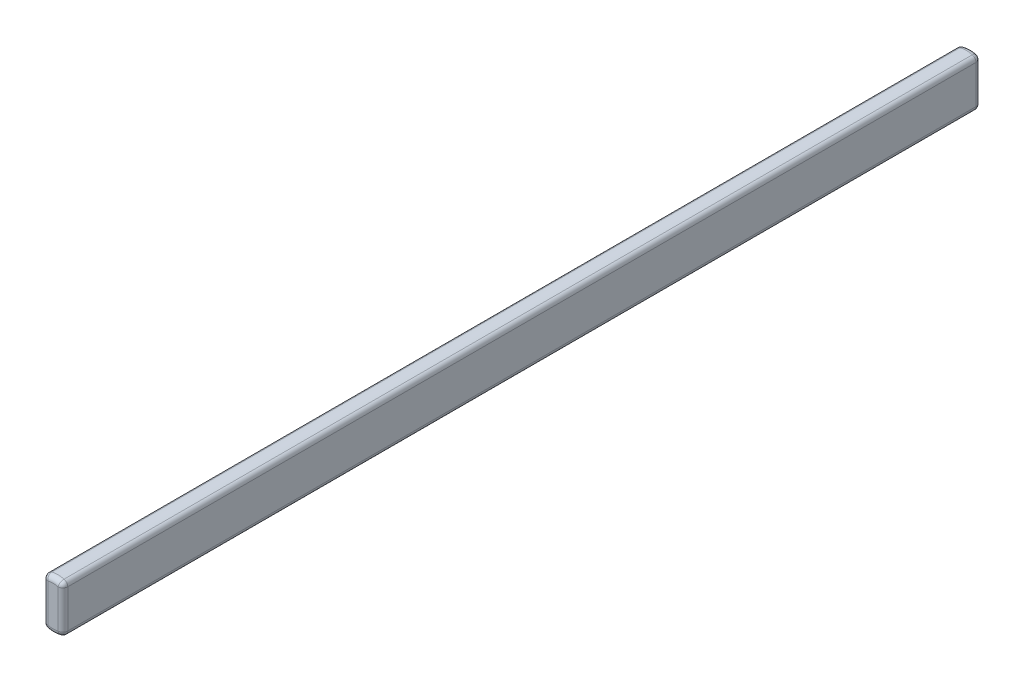
SolidWorks part; units mm, degrees
material "PET"
ref_plane "Front Plane" through (0, 0, 0) normal (0, 0, 1) x (1, 0, 0)
ref_plane "Top Plane" through (0, 0, 0) normal (0, 1, 0) x (1, 0, 0)
ref_plane "Right Plane" through (0, 0, 0) normal (1, 0, 0) x (0, 0, -1)
sketch "Sketch1" plane through (0, 0, 0) normal (0, 0, 1) x (1, 0, 0)
  circle A0 centre (0, 0) radius 5
  dimension "D1" = 10
extrude "Boss-Extrude1" add sketch "Sketch1" along normal blind 170
sketch "Sketch2" plane through (0, 0, 0) normal (0, 0, -1) x (-1, 0, 0)
  line L1 (-2, -4.5826) -> (2, -4.5826) construction
  line L2 (-2, -4.5826) -> (-2, 4.5826)
  line L3 (-2, 4.5826) -> (2, 4.5826) construction
  line L4 (2, -4.5826) -> (2, 4.5826)
  line L5 (-2, -4.5826) -> (2, 4.5826) construction
  line L6 (-2, 4.5826) -> (2, -4.5826) construction
  arc A1 (2, 4.5826) -> (-2, 4.5826) centre (0, 0) ccw
  circle A2 centre (0, 0) radius 5
  arc A3 (-2, -4.5826) -> (2, -4.5826) centre (0, 0) ccw
  dimension "D1" = 0
  dimension "D2" = 4
extrude "Boss-Extrude2" add sketch "Sketch2" along normal blind 8
sketch "Sketch5" plane through (0, 0, 170) normal (0, 0, 1) x (1, 0, 0)
  line L4 (2, -4.5826) -> (2, 4.5826)
  line L5 (-2, 4.5826) -> (-2, -4.5826)
  circle A0 centre (0, 0) radius 5 construction
  arc A4 (2, 4.5826) -> (-2, 4.5826) centre (0, 0) ccw
  arc A5 (-2, -4.5826) -> (2, -4.5826) centre (0, 0) ccw
  dimension "D1" = 4
extrude "Boss-Extrude3" add sketch "Sketch5" along normal blind 8
fillet "Fillet4" radius 1 16 edges at (-2, 0, -8) (0, -5, -8) (2, 0, -8) (0, 5, -8) (-2, 4.5826, -4) (-2, -4.5826, -4) (2, -4.5826, -4) (2, 4.5826, -4) (2, 0, 178) (0, -5, 178) (-2, 0, 178) (0, 5, 178) (2, 4.5826, 174) (-2, -4.5826, 174) (-2, 4.5826, 174) (2, -4.5826, 174)
sketch "Sketch7" plane through (0, 0, 170) normal (0, 0, 1) x (1, 0, 0)
  line L0 (-2, -3.873) -> (-2, 3.873) construction
  line L1 (2, 3.873) -> (2, -3.873) construction
  line L2 (-2, -3.873) -> (-2, 3.873)
  line L3 (2, 3.873) -> (2, -3.873)
  arc A0 (-1.25, 4.8412) -> (-2, 3.873) centre (-1, 3.873) ccw construction
  arc A1 (-1.25, 4.8412) -> (-1.25, -4.8412) centre (0, 0) ccw construction
  arc A2 (-2, -3.873) -> (-1.25, -4.8412) centre (-1, -3.873) ccw construction
  arc A3 (1.25, -4.8412) -> (2, -3.873) centre (1, -3.873) ccw construction
  arc A4 (1.25, -4.8412) -> (1.25, 4.8412) centre (0, 0) ccw construction
  arc A5 (2, 3.873) -> (1.25, 4.8412) centre (1, 3.873) ccw construction
  arc A6 (-1.25, 4.8412) -> (-2, 3.873) centre (-1, 3.873) ccw
  arc A7 (-1.25, 4.8412) -> (-1.25, -4.8412) centre (0, 0) ccw
  arc A8 (-2, -3.873) -> (-1.25, -4.8412) centre (-1, -3.873) ccw
  arc A9 (1.25, -4.8412) -> (2, -3.873) centre (1, -3.873) ccw
  arc A10 (1.25, -4.8412) -> (1.25, 4.8412) centre (0, 0) ccw
  arc A11 (2, 3.873) -> (1.25, 4.8412) centre (1, 3.873) ccw
extrude "Cut-Extrude1" cut sketch "Sketch7" against normal through all
